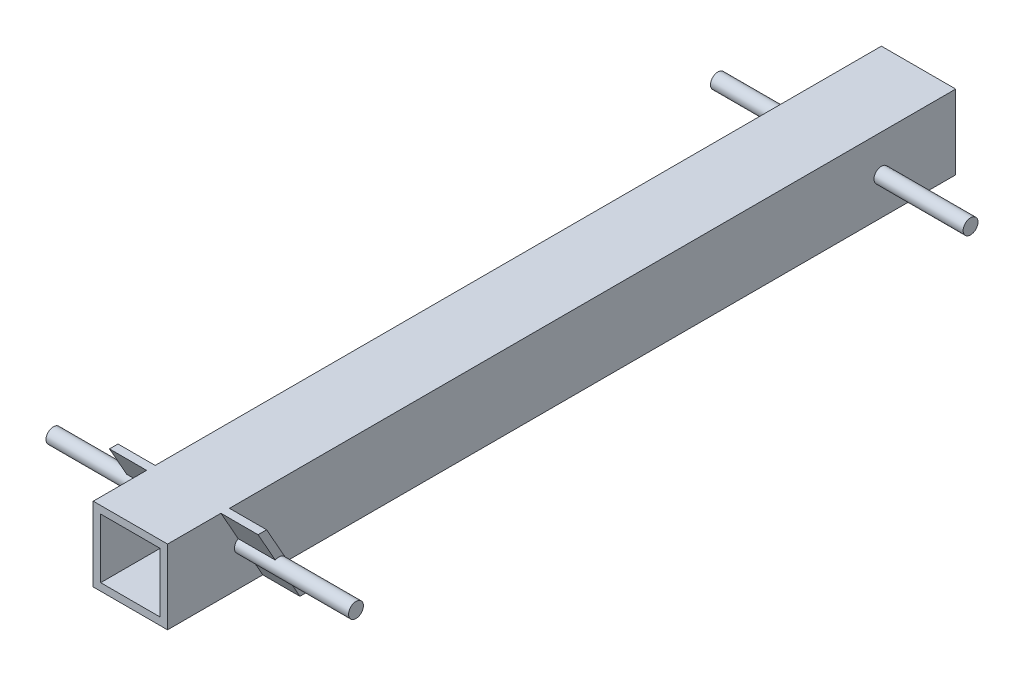
SolidWorks part; units mm, degrees
ref_plane "前视基准面" through (0, 0, 0) normal (0, 0, 1) x (1, 0, 0)
ref_plane "上视基准面" through (0, 0, 0) normal (0, 1, 0) x (1, 0, 0)
ref_plane "右视基准面" through (0, 0, 0) normal (1, 0, 0) x (0, 0, -1)
sketch "草图1" plane through (0, 0, 0) normal (0, 0, 1) x (1, 0, 0)
  line L1 (0, 0) -> (10, 0)
  line L2 (0, 0) -> (0, 10)
  line L3 (0, 10) -> (10, 10)
  line L4 (10, 0) -> (10, 10)
  line L5 (1, 1) -> (9, 1)
  line L6 (1, 1) -> (1, 9)
  line L7 (1, 9) -> (9, 9)
  line L8 (9, 1) -> (9, 9)
  point P5 (1, 1)
extrude "凸台-拉伸1" add sketch "草图1" along normal blind 106.066
sketch "草图2" plane through (10, 0, 0) normal (1, 0, 0) x (0, 0, -1)
  circle A0 centre (-10, 5) radius 1
  point P0 (-10, 5)
extrude "切除-拉伸1" cut sketch "草图2" against normal blind 10
sketch "草图5" plane through (10, 0, 0) normal (1, 0, 0) x (0, 0, -1)
  point P0 (-10, 5)
  circle M2 centre (-10, 5) radius 1
extrude "凸台-拉伸3" add sketch "草图5" against normal blind 22 and the other way blind 12 contours M2 region at (10, 5, 10)
sketch "草图9" plane through (10, 0, 0) normal (1, 0, 0) x (0, 0, -1)
  line L0 (-106.066, 0) -> (-106.066, 10) construction
  circle A0 centre (-106.066, 5) radius 10
  circle A1 centre (-96.066, 5) radius 1
  point P0 (-106.066, 5)
extrude "凸台-拉伸7" add sketch "草图9" against normal blind 25.36 and the other way blind 15.36 contours A0 A1 | A0 A1 region at (10, 5, 96.4993) region at (10, 5, 95.6507)
sketch "草图10" plane through (10, 0, 0) normal (1, 0, 0) x (0, 0, -1)
  line L0 (-96.066, 5) -> (-96.066, 10)
  line L1 (-106.066, 10) -> (0, 10) construction
  line L2 (-96.066, 10) -> (-98.881, 10)
  line L3 (-98.881, 10) -> (-96.066, 5)
  line L4 (-96.066, 5) -> (-93.251, 0)
  line L5 (-106.066, 0) -> (0, 0) construction
  line L6 (-93.251, 0) -> (-92.3796, 0.4906)
  line L7 (-92.3796, 0.4906) -> (-97.7334, 10)
  line L8 (-97.7334, 10) -> (-98.881, 10)
  line L9 (-92.3796, 0.4906) -> (-92.1034, 0)
  line L10 (-92.1034, 0) -> (-93.251, 0)
  point P0 (-96.066, 5)
  circle M1 centre (-96.066, 5) radius 1
  line M6 (-106.066, 0) -> (0, 0)
extrude "凸台-拉伸8" add sketch "草图10" along normal blind 5 and the other way blind 15 contours L0 L7 L2 L3 M1 | L7 L0 M1 | L0 L4 M1 | L3 L0 M1 | L6 L7 L4 M1 | L9 L6 M6 region at (10, 5.6378, 96.2332) region at (10, 5.1244, 95.5914) region at (10, 8.1045, 97.2692) region at (10, 6.276, 95.8205) region at (10, 2.4134, 94.0222) region at (10, 0.1635, 92.578)
